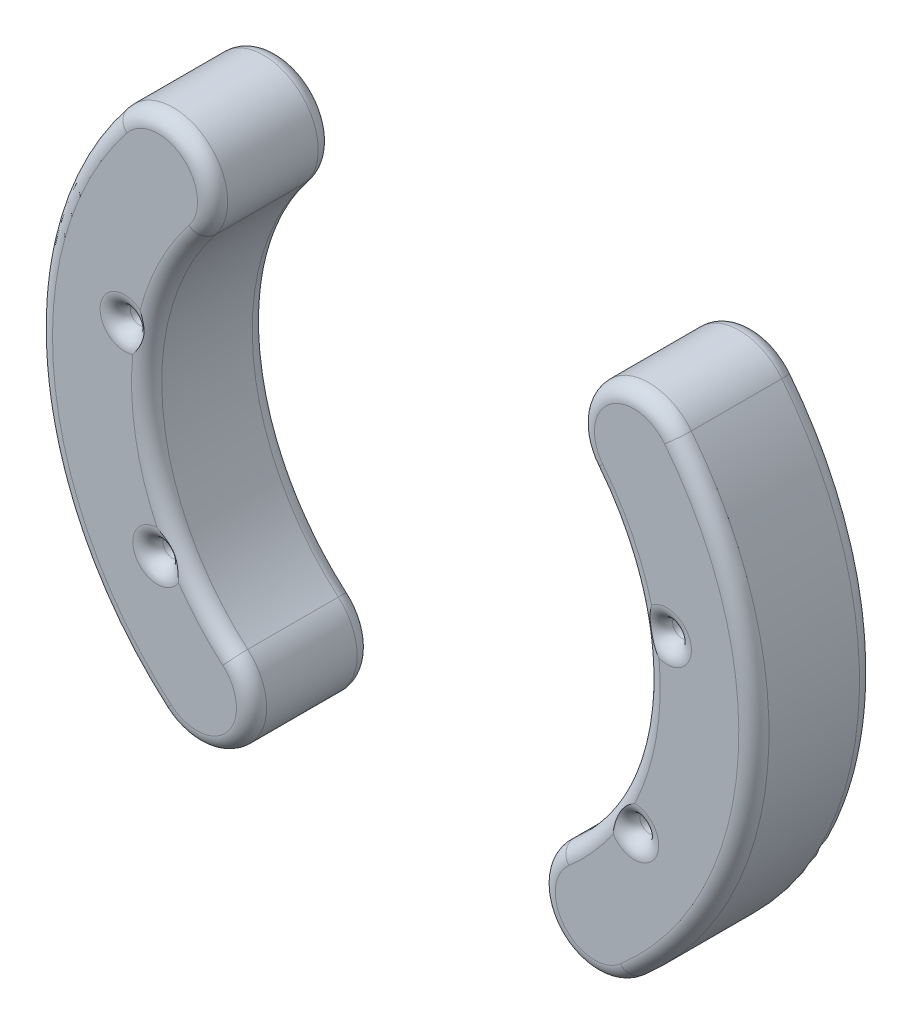
SolidWorks part; units mm, degrees
material "6061-O (SS)"
ref_plane "前视基准面" through (0, 0, 0) normal (0, 0, 1) x (1, 0, 0)
ref_plane "上视基准面" through (0, 0, 0) normal (0, 1, 0) x (1, 0, 0)
ref_plane "右视基准面" through (0, 0, 0) normal (1, 0, 0) x (0, 0, -1)
other "Configuration Table"
sketch "草图1" plane through (0, 0, 0) normal (0, 0, 1) x (1, 0, 0)
  line L0 (0, 0) -> (0, -21.9886) construction
  line L1 (0, 0) -> (-15.3152, -15.3152) construction
  line L2 (0, 0) -> (17.1443, -17.1443) construction
  line L3 (0, 50.5605) -> (0, -381.1612) construction
  line L4 (0, 0) -> (-15.4548, -4.1411) construction
  line L5 (-15.3152, -162.7971) -> (15.3152, -162.7971) construction
  line L6 (-14.4426, -147.3648) -> (-22.6976, -12.3955)
  line L7 (-13.5404, -162.1157) -> (0, -200.0384) construction
  line L8 (14.4404, -147.3996) -> (22.6976, -12.3955)
  line L9 (0, -200.0384) -> (13.5404, -162.1157) construction
  line L13 (26.3611, -230.4779) -> (-26.3611, -230.4779) construction
  circle A0 centre (0, 0) radius 16 construction
  circle A1 centre (0, 0) radius 12.75
  circle A2 centre (-11.3137, -11.3137) radius 1.65
  circle A3 centre (0, -16) radius 1.65
  circle A4 centre (11.3137, -11.3137) radius 1.65
  arc A6 (-10.1423, -7.7263) -> (-22.6976, -12.3955) centre (-15.7107, -11.9682) ccw
  arc A7 (10.1423, -7.7263) -> (22.6976, -12.3955) centre (15.7107, -11.9682) cw
  circle A8 centre (0, -200.0384) radius 33.0276 construction
  circle A10 centre (0, -200.0384) radius 40.2675 construction
  arc A11 (-15.3152, -162.7971) -> (-26.3611, -230.4779) centre (0, -200.0384) ccw construction
  arc A12 (-18.0688, -156.1013) -> (-31.1007, -235.9508) centre (0, -200.0384) ccw construction
  arc A13 (-12.5616, -169.4929) -> (-21.6215, -225.0051) centre (0, -200.0384) ccw construction
  arc A14 (-12.5616, -169.4929) -> (-18.0688, -156.1013) centre (-15.3152, -162.7971) ccw construction
  arc A15 (-31.1007, -235.9508) -> (-21.6215, -225.0051) centre (-26.3611, -230.4779) ccw construction
  arc A16 (15.3152, -162.7971) -> (26.3611, -230.4779) centre (0, -200.0384) cw construction
  arc A17 (31.0795, -235.9263) -> (18.0565, -156.1313) centre (0, -200.0384) ccw construction
  arc A18 (21.6427, -225.0296) -> (12.574, -169.4629) centre (0, -200.0384) ccw construction
  arc A19 (21.6427, -225.0296) -> (31.0795, -235.9263) centre (26.3611, -230.4779) ccw construction
  arc A20 (18.0565, -156.1313) -> (12.574, -169.4629) centre (15.3152, -162.7971) ccw construction
  arc A21 (-20.1768, -157.0286) -> (-31.1007, -235.9508) centre (0, -200.0384) ccw
  arc A22 (-21.6215, -225.0051) -> (-31.1007, -235.9508) centre (-26.3611, -230.4779) cw
  arc A23 (-21.6215, -225.0051) -> (-16.5415, -171.4516) centre (0, -200.0384) cw
  arc A24 (16.5459, -171.4167) -> (21.6427, -225.0296) centre (0, -200.0384) cw
  arc A25 (21.6427, -225.0296) -> (31.0795, -235.9263) centre (26.3611, -230.4779) ccw
  arc A26 (31.0795, -235.9263) -> (20.1727, -157.0624) centre (0, -200.0384) ccw
  arc A27 (-14.4426, -147.3648) -> (-20.1768, -157.0286) centre (-24.4239, -147.9753) cw
  arc A28 (14.4404, -147.3996) -> (20.1727, -157.0624) centre (24.4218, -148.01) ccw
  arc A29 (-11.9982, -165.7569) -> (12.0041, -165.7364) centre (0.0062, -169.4779) cw
  arc A30 (-16.5415, -171.4516) -> (-11.9982, -165.7569) centre (-21.5498, -162.7962) ccw
  arc A31 (12.0041, -165.7364) -> (16.5459, -171.4167) centre (21.5507, -162.7593) ccw
  point P15 (0, -220)
  point P22 (0, -220)
  point P30 (0, -165.3003)
  point P33 (0, -163.5756)
  point P35 (-39.7417, -193.5524)
  point P41 (39.7417, -193.5524)
  point P68 (-12.5616, -169.4929)
  point P71 (12.574, -169.4629)
  dimension "D1" = 32
  dimension "D2" = 25.5
  dimension "D5" = 3.3
  dimension "D6" = 3.3
  dimension "D7" = 3.3
  dimension "D12" = 14
  dimension "D8" = 10
  dimension "D10" = 10
  dimension "D11" = 10
  dimension "D13" = 10
  dimension "D3" = 45
  dimension "D4" = 45
  dimension "D9" = 75
extrude "凸台-拉伸1" add sketch "草图1" along normal blind 19 contours A1 L6 A4 A3 A2 region at (-0.0249, -115.9056, 0)
sketch "草图4" plane through (0, 0, 0) normal (0, 0, -1) x (-1, 0, 0)
  line L0 (-13.7159, -28.2019) -> (-10.1137, -87.0977)
  line L1 (-14.4404, -147.3996) -> (-22.6976, -12.3955) construction
  line L2 (0, 41.4898) -> (0, 27) construction
  line L3 (2.2925, -97.284) -> (9.4118, -88.8496)
  line L4 (0, -27) -> (0, -178.2536) construction
  line L5 (-2.2925, -97.284) -> (-9.4118, -88.8496)
  line L6 (13.7159, -28.2019) -> (10.1137, -87.0977)
  arc A0 (-9.6494, -25.2169) -> (9.6494, -25.2169) centre (0, 0) ccw
  arc A1 (13.7159, -28.2019) -> (9.6494, -25.2169) centre (10.7215, -28.0187) ccw
  arc A2 (-13.7159, -28.2019) -> (-9.6494, -25.2169) centre (-10.7215, -28.0187) cw
  arc A3 (9.4118, -88.8496) -> (10.1137, -87.0977) centre (7.1193, -86.9146) ccw
  arc A4 (2.2925, -97.284) -> (-2.2925, -97.284) centre (0, -95.349) cw
  arc A5 (-10.1137, -87.0977) -> (-9.4118, -88.8496) centre (-7.1193, -86.9146) ccw
  point P15 (14.0299, -23.0686)
  point P18 (-14.0299, -23.0686)
  point P22 (10.053, -88.09)
  point P25 (0, -100)
  point P28 (-10.053, -88.09)
  dimension "D2" = 54
  dimension "D3" = 3
  dimension "D6" = 3
  dimension "D1" = 8
  dimension "D4" = 100
  dimension "D5" = 60
extrude "切除-拉伸2" cut sketch "草图4" against normal blind 48
sketch "草图5" plane through (0, 0, 19) normal (0, 0, 1) x (1, 0, 0)
  line L0 (-12.2411, -94.7997) -> (-2.2925, -106.5861) construction
  line L1 (-9.4118, -88.8496) -> (-2.2925, -97.284) construction
  line L2 (-14.4426, -147.3648) -> (-22.6976, -12.3955) construction
  line L3 (-8.4988, -198.4027) -> (8.4988, -198.4027) construction
  line L4 (-17.528, -96.9179) -> (-11.4932, -195.5858) construction
  line L6 (17.528, -96.9179) -> (11.4932, -195.5858) construction
  line L7 (12.2411, -94.7997) -> (2.2925, -106.5861) construction
  line L8 (0, -107.651) -> (0, -201.1469) construction
  circle A0 centre (0, -188.4027) radius 2.1
  arc A1 (11.4932, -195.5858) -> (8.4988, -198.4027) centre (8.4988, -195.4027) cw construction
  arc A2 (-8.4988, -198.4027) -> (-11.4932, -195.5858) centre (-8.4988, -195.4027) cw construction
  arc A3 (2.2925, -106.5861) -> (-2.2925, -106.5861) centre (0, -104.651) cw construction
  arc A4 (17.528, -96.9179) -> (12.2411, -94.7997) centre (14.5336, -96.7348) ccw construction
  arc A5 (-12.2411, -94.7997) -> (-17.528, -96.9179) centre (-14.5336, -96.7348) ccw construction
  circle A6 centre (0, -118.4027) radius 2.1
  point P12 (-11.3209, -198.4027)
  point P23 (-18.0807, -87.8814)
  dimension "D2" = 3
  dimension "D3" = 4.2
  dimension "D4" = 4.2
  dimension "D5" = 10
  dimension "D6" = 70
  dimension "D1" = 6
extrude "切除-拉伸4" cut sketch "草图5" against normal blind 30
sketch "草图3" plane through (0, 0, 19) normal (0, 0, 1) x (1, 0, 0)
  line L0 (-10, -220) -> (-9.806, -223.1719)
  line L3 (0, -220) -> (0, -221.5633) construction
  line L5 (10, -220) -> (9.806, -223.1719)
  line L6 (-14.4426, -147.3648) -> (-22.6976, -12.3955) construction
  line L10 (-22.6976, -12.3955) -> (-14.4426, -147.3648)
  line L12 (14.4404, -147.3996) -> (22.6976, -12.3955)
  line L13 (-22.6976, -12.3955) -> (-14.4426, -147.3648)
  line L15 (14.4404, -147.3996) -> (22.6976, -12.3955)
  arc A0 (8.2741, -223.9564) -> (-8.2741, -223.9564) centre (0, -237.0633) ccw
  arc A1 (-9.806, -223.1719) -> (-8.2741, -223.9564) centre (-8.8079, -223.1108) ccw
  arc A2 (9.806, -223.1719) -> (8.2741, -223.9564) centre (8.8079, -223.1108) cw
  arc A6 (22.6976, -12.3955) -> (10.1423, -7.7263) centre (15.7107, -11.9682) ccw
  arc A7 (-10.1423, -7.7263) -> (10.1423, -7.7263) centre (0, 0) ccw
  arc A8 (-10.1423, -7.7263) -> (-22.6976, -12.3955) centre (-15.7107, -11.9682) ccw
  arc A9 (22.6976, -12.3955) -> (10.1423, -7.7263) centre (15.7107, -11.9682) ccw
  arc A10 (-10.1423, -7.7263) -> (10.1423, -7.7263) centre (0, 0) ccw
  arc A11 (-10.1423, -7.7263) -> (-22.6976, -12.3955) centre (-15.7107, -11.9682) ccw
  arc A23 (12.0041, -165.7364) -> (-11.9982, -165.7569) centre (0.0062, -169.4779) ccw
  arc A24 (12.0041, -165.7364) -> (-11.9982, -165.7569) centre (0.0062, -169.4779) ccw
  arc A25 (12.0041, -165.7364) -> (16.5459, -171.4167) centre (21.5507, -162.7593) ccw
  arc A26 (12.0041, -165.7364) -> (16.5459, -171.4167) centre (21.5507, -162.7593) ccw
  arc A27 (21.6427, -225.0296) -> (16.5459, -171.4167) centre (0, -200.0384) ccw
  arc A28 (21.6427, -225.0296) -> (16.5459, -171.4167) centre (0, -200.0384) ccw
  arc A29 (21.6427, -225.0296) -> (31.0795, -235.9263) centre (26.3611, -230.4779) ccw
  arc A30 (21.6427, -225.0296) -> (31.0795, -235.9263) centre (26.3611, -230.4779) ccw
  arc A31 (31.0795, -235.9263) -> (20.1727, -157.0624) centre (0, -200.0384) ccw
  arc A32 (31.0795, -235.9263) -> (20.1727, -157.0624) centre (0, -200.0384) ccw
  arc A33 (14.4404, -147.3996) -> (20.1727, -157.0624) centre (24.4218, -148.01) ccw
  arc A34 (14.4404, -147.3996) -> (20.1727, -157.0624) centre (24.4218, -148.01) ccw
  arc A35 (-20.1768, -157.0286) -> (-14.4426, -147.3648) centre (-24.4239, -147.9753) ccw
  arc A36 (-20.1768, -157.0286) -> (-14.4426, -147.3648) centre (-24.4239, -147.9753) ccw
  arc A37 (-20.1768, -157.0286) -> (-31.1007, -235.9508) centre (0, -200.0384) ccw
  arc A38 (-20.1768, -157.0286) -> (-31.1007, -235.9508) centre (0, -200.0384) ccw
  arc A39 (-31.1007, -235.9508) -> (-21.6215, -225.0051) centre (-26.3611, -230.4779) ccw
  arc A40 (-31.1007, -235.9508) -> (-21.6215, -225.0051) centre (-26.3611, -230.4779) ccw
  arc A41 (-16.5415, -171.4516) -> (-21.6215, -225.0051) centre (0, -200.0384) ccw
  arc A42 (-16.5415, -171.4516) -> (-21.6215, -225.0051) centre (0, -200.0384) ccw
  arc A43 (-16.5415, -171.4516) -> (-11.9982, -165.7569) centre (-21.5498, -162.7962) ccw
  arc A44 (-16.5415, -171.4516) -> (-11.9982, -165.7569) centre (-21.5498, -162.7962) ccw
  dimension "D1" = 31
  dimension "D2" = 2
  dimension "D3" = 3.1778
  dimension "D4" = 0
ref_plane "基准面1" through (0, 0, 19) normal (0, 0, 1) x (1, 0, 0)
sketch "草图7" plane through (0, 0, 19) normal (0, 0, 1) x (1, 0, 0)
  circle A0 centre (0, -200.0384) radius 36.5 construction
  circle A1 centre (0, -163.5384) radius 1.25
  circle A2 centre (23.4617, -172.0778) radius 1.25
  circle A3 centre (35.9455, -193.7003) radius 1.25
  circle A4 centre (31.6099, -218.2884) radius 1.25
  circle A5 centre (12.4837, -234.3372) radius 1.25
  circle A6 centre (-12.4837, -234.3372) radius 1.25
  circle A7 centre (-31.6099, -218.2884) radius 1.25
  circle A8 centre (-35.9455, -193.7003) radius 1.25
  circle A9 centre (-23.4617, -172.0778) radius 1.25
  dimension "D1" = 9
extrude "切除-拉伸5" cut sketch "草图7" against normal blind 32
ref_plane "基准面2" through (0, 0, 19) normal (0, 0, 1) x (1, 0, 0)
sketch "草图10" plane through (0, 0, 19) normal (0, 0, 1) x (1, 0, 0)
  line L0 (-22.6976, -12.3955) -> (-14.4426, -147.3648)
  line L1 (22.6976, -12.3955) -> (14.4404, -147.3996)
  line L2 (-49.9336, -183.21) -> (49.9459, -183.21) construction
  arc A0 (-10.1423, -7.7263) -> (-22.6976, -12.3955) centre (-15.7107, -11.9682) ccw
  arc A1 (-10.1423, -7.7263) -> (10.1423, -7.7263) centre (0, 0) ccw
  arc A2 (10.1423, -7.7263) -> (22.6976, -12.3955) centre (15.7107, -11.9682) cw
  arc A3 (-20.1768, -157.0286) -> (-14.4426, -147.3648) centre (-24.4239, -147.9753) ccw
  arc A4 (14.4404, -147.3996) -> (20.1727, -157.0624) centre (24.4218, -148.01) ccw
  arc A5 (-11.9982, -165.7569) -> (12.0041, -165.7364) centre (0.0062, -169.4779) cw
  arc A6 (16.5459, -171.4167) -> (12.0041, -165.7364) centre (21.5507, -162.7593) cw
  arc A7 (-11.9982, -165.7569) -> (-16.5415, -171.4516) centre (-21.5499, -162.7962) cw
  arc A8 (-16.5415, -171.4516) -> (-25.8541, -179.4862) centre (0.0001, -200.0385) ccw
  arc A9 (-16.5415, -171.4516) -> (-21.6215, -225.0051) centre (0, -200.0384) ccw construction
  arc A10 (16.5459, -171.4167) -> (25.8954, -179.4862) centre (-0.0001, -200.0385) cw
  arc A11 (21.6427, -225.0296) -> (16.5459, -171.4167) centre (0, -200.0384) ccw construction
  arc A12 (25.8954, -179.4862) -> (37.1865, -170.525) centre (31.5409, -175.0056) cw
  arc A13 (31.0795, -235.9263) -> (20.1727, -157.0624) centre (0, -200.0384) ccw construction
  arc A14 (-25.8541, -179.4862) -> (-37.1888, -170.4759) centre (-31.5215, -174.9811) ccw
  arc A15 (-20.1768, -157.0286) -> (-31.1007, -235.9508) centre (0, -200.0384) ccw construction
  arc A16 (-20.1768, -157.0286) -> (-37.1888, -170.4759) centre (0, -200.0384) ccw
  arc A17 (20.1727, -157.0624) -> (37.1865, -170.525) centre (0, -200.0384) cw
  point P35 (0.0062, -183.21)
extrude "切除-拉伸7" cut sketch "草图10" against normal blind 16
ref_plane "基准面4" through (0, 0, 0) normal (0, 0, -1) x (-1, 0, 0)
ref_plane "基准面5" through (0, 0, 0) normal (0, 0, -1) x (-1, 0, 0)
sketch "草图12" plane through (0, 0, 0) normal (0, 0, -1) x (-1, 0, 0)
  line L0 (-0.0062, -169.4779) -> (-0.0062, -196.3706) construction
  circle A0 centre (30.2561, -171.2616) radius 1.5
  circle A1 centre (-30.2684, -171.2616) radius 1.5
extrude "切除-拉伸9" cut sketch "草图12" against normal blind 10
ref_plane "基准面6" through (0, 0, 0) normal (0, 0, -1) x (-1, 0, 0)
ref_plane "基准面7" through (0, 0, 0) normal (0, 0, -1) x (-1, 0, 0)
sketch "草图14" plane through (0, 0, 0) normal (0, 0, -1) x (-1, 0, 0)
  line L0 (-22.6976, -12.3955) -> (-14.4404, -147.3996)
  line L1 (14.4426, -147.3648) -> (22.6976, -12.3955)
  arc A0 (-10.1423, -7.7263) -> (10.1423, -7.7263) centre (0, 0) ccw
  arc A1 (10.1423, -7.7263) -> (22.6976, -12.3955) centre (15.7107, -11.9682) cw
  arc A2 (-10.1423, -7.7263) -> (-22.6976, -12.3955) centre (-15.7107, -11.9682) ccw
  arc A3 (-14.4404, -147.3996) -> (-20.1727, -157.0624) centre (-24.4218, -148.01) cw
  arc A4 (14.4426, -147.3648) -> (20.1768, -157.0286) centre (24.4239, -147.9753) ccw
  arc A5 (20.1768, -157.0286) -> (31.1007, -235.9508) centre (0, -200.0384) cw
  arc A6 (31.1007, -235.9508) -> (21.6215, -225.0051) centre (26.3611, -230.4779) cw
  arc A7 (21.6215, -225.0051) -> (16.5415, -171.4516) centre (0, -200.0384) ccw
  arc A8 (16.5415, -171.4516) -> (11.9982, -165.7569) centre (21.5498, -162.7962) cw
  arc A9 (11.9982, -165.7569) -> (-12.0041, -165.7364) centre (-0.0062, -169.4779) ccw
  arc A10 (-12.0041, -165.7364) -> (-16.5459, -171.4167) centre (-21.5507, -162.7593) cw
  arc A11 (-16.5459, -171.4167) -> (-21.6427, -225.0296) centre (0, -200.0384) ccw
  arc A12 (-21.6427, -225.0296) -> (-31.0795, -235.9263) centre (-26.3611, -230.4779) cw
  arc A13 (-31.0795, -235.9263) -> (-20.1727, -157.0624) centre (0, -200.0384) cw
extrude "切除-拉伸10" cut sketch "草图14" against normal blind 3
fillet "圆角1" radius 2 7 edges at (20.9127, -235.1963, 3) (47.2694, -204.4523, 3) (27.0603, -169.3601, 3) (30.3599, -218.2884, 3) (34.6955, -193.7003, 3) (28.7684, -171.2616, 3)
fillet "圆角2" radius 2 7 edges at (-47.3033, -204.4369, 3) (-20.8883, -235.2175, 3) (-27.0163, -169.3137, 3) (-37.1955, -193.7003, 3) (-32.8599, -218.2884, 3) (-31.7561, -171.2616, 3)
fillet "圆角3" radius 2 6 edges at (32.8599, -218.2884, 19) (37.1955, -193.7003, 19) (47.2694, -204.4523, 19) (20.9127, -235.1963, 19) (32.9168, -203.1121, 19) (27.0603, -169.3601, 19)
fillet "圆角4" radius 2 6 edges at (-30.3599, -218.2884, 19) (-34.6955, -193.7003, 19) (-32.8858, -203.0963, 19) (-20.8883, -235.2175, 19) (-47.3033, -204.4369, 19) (-27.0163, -169.3137, 19)
